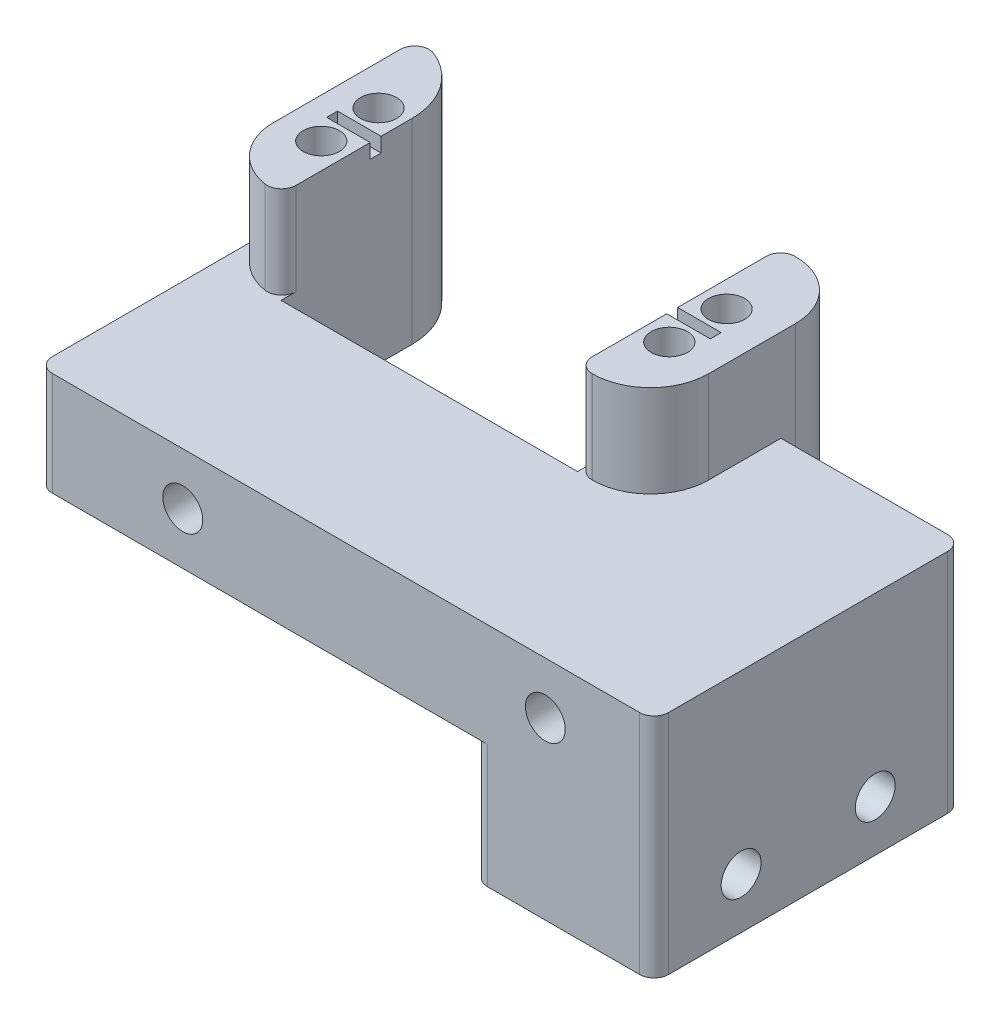
SolidWorks part; units mm, degrees
ref_plane "Front" through (0, 0, 0) normal (0, 0, 1) x (1, 0, 0)
ref_plane "Top" through (0, 0, 0) normal (0, 1, 0) x (1, 0, 0)
ref_plane "Right" through (0, 0, 0) normal (1, 0, 0) x (0, 0, -1)
sketch "Sketch1" plane through (0, 0, 0) normal (0, 1, 0) x (1, 0, 0)
  line L1 (0, 0) -> (85, 0)
  line L2 (0, 0) -> (0, 52.5)
  line L3 (0, 52.5) -> (85, 52.5)
  line L4 (85, 0) -> (85, 52.5)
  dimension "D1" = 85
  dimension "D2" = 52.5
extrude "Boss-Extrude1" add sketch "Sketch1" along normal blind 27
sketch "Sketch2" plane through (0, 27, 0) normal (0, 1, 0) x (1, 0, 0)
  line L0 (0, 52.5) -> (0, 0) construction
  line L1 (85, 52.5) -> (0, 52.5) construction
  circle A0 centre (5.5, 41.5) radius 2.5
  circle A1 centre (53.5, 41.5) radius 2.5
  circle A2 centre (53.5, 33.6) radius 2.5
  circle A3 centre (5.5, 33.6) radius 2.5
  dimension "D3" = 5
  dimension "D6" = 48
  dimension "D1" = 5.5
  dimension "D2" = 11
  dimension "D7" = 7.9
  dimension "D4" = 2
  dimension "D5" = 2
extrude "Cut-Extrude1" cut sketch "Sketch2" against normal through all
sketch "Sketch4" plane through (0, 0, 0) normal (-1, 0, 0) x (0, 0, 1)
  line L0 (-52.5, 27) -> (0, 27) construction
  line L1 (0, 27) -> (-24.5, 27)
  line L2 (0, 27) -> (0, 14.3)
  line L3 (0, 14.3) -> (-24.5, 14.3)
  line L4 (-24.5, 27) -> (-24.5, 14.3)
  line L5 (0, 27) -> (0, 0) construction
  dimension "D1" = 12.7
  dimension "D2" = 24.5
extrude "Cut-Extrude2" cut sketch "Sketch4" against normal through all
sketch "Sketch5" plane through (0, 0, -24.5) normal (0, 0, 1) x (1, 0, 0)
  line L0 (85, 14.3) -> (0, 14.3) construction
  line L1 (85, 27) -> (60, 27)
  line L2 (85, 27) -> (85, 14.3)
  line L3 (85, 14.3) -> (60, 14.3)
  line L4 (60, 27) -> (60, 14.3)
  dimension "D1" = 25
extrude "Cut-Extrude3" cut sketch "Sketch5" against normal through all
sketch "Sketch6" plane through (0, 27, 0) normal (0, 1, 0) x (1, 0, 0)
  line L0 (60, 24.5) -> (0, 24.5) construction
  line L1 (9.05, 24.5) -> (49.95, 24.5)
  line L2 (9.05, 24.5) -> (9.05, 52.5)
  line L3 (9.05, 52.5) -> (49.95, 52.5)
  line L4 (49.95, 24.5) -> (49.95, 52.5)
  line L5 (60, 52.5) -> (0, 52.5) construction
  line L6 (29.5, 41.5) -> (29.5, 52.5) construction
  line L7 (5.5, 41.5) -> (53.5, 41.5) construction
  circle A0 centre (5.5, 41.5) radius 2.5 construction
  dimension "D1" = 3.55
extrude "Cut-Extrude4" cut sketch "Sketch6" against normal through all
fillet "Fillet1" radius 10 1 edges at (9.05, 13.5, -52.5)
fillet "Fillet2" radius 8 3 edges at (60, 20.65, -52.5) (0, 20.65, -24.5) (60, 20.65, -24.5)
fillet "Fillet4" radius 2 7 edges at (9.05, 20.65, -24.5) (49.95, 20.65, -24.5) (49.95, 13.5, -52.5) (85, 7.15, -52.5) (85, 7.15, 0) (0, 7.15, 0) (0, 13.5, -52.5)
sketch "Sketch7" plane through (0, 0, 0) normal (0, 0, 1) x (1, 0, 0)
  line L0 (20, 0) -> (20, 14.3) construction
  line L1 (2, 0) -> (83, 0) construction
  line L2 (83, 14.3) -> (2, 14.3) construction
  line L3 (85, 14.3) -> (85, 0) construction
  circle A0 centre (70, 7.15) radius 2.75
  circle A1 centre (20, 7.15) radius 2.75
  dimension "D3" = 5.5
  dimension "D1" = 50
  dimension "D2" = 15
extrude "Cut-Extrude5" cut sketch "Sketch7" against normal through all
sketch "Sketch8" plane through (0, 27, 0) normal (0, 1, 0) x (1, 0, 0)
  line L0 (9.05, 42.5452) -> (9.05, 26.5757) construction
  line L1 (3.05, 38.3) -> (9.05, 38.3)
  line L2 (3.05, 38.3) -> (3.05, 36.8)
  line L3 (3.05, 36.8) -> (9.05, 36.8)
  line L4 (9.05, 38.3) -> (9.05, 36.8)
  line L5 (5.5, 39) -> (5.5, 36.1) construction
  line L6 (5.5, 37.55) -> (9.05, 37.55) construction
  line L7 (49.95, 26.5) -> (49.95, 50.5) construction
  line L8 (49.95, 36.8) -> (55.95, 36.8)
  line L9 (49.95, 36.8) -> (49.95, 38.3)
  line L10 (49.95, 38.3) -> (55.95, 38.3)
  line L11 (55.95, 36.8) -> (55.95, 38.3)
  circle A0 centre (5.5, 41.5) radius 2.5 construction
  circle A1 centre (5.5, 33.6) radius 2.5 construction
  dimension "D1" = 1.5
  dimension "D2" = 6
extrude "Cut-Extrude6" cut sketch "Sketch8" against normal blind 2
sketch "Sketch9" plane through (0, 14.3, 0) normal (0, 1, 0) x (1, 0, 0)
  line L0 (85, 50.5) -> (85, 2) construction
  line L1 (85, 42.5) -> (60, 42.5)
  line L2 (85, 42.5) -> (85, 52.5)
  line L3 (85, 52.5) -> (83, 52.5)
  line L4 (60, 42.5) -> (60, 44.5)
  line L5 (52, 52.5) -> (83, 52.5) construction
  line L6 (52, 52.5) -> (83, 52.5)
  arc A0 (60, 44.5) -> (52, 52.5) centre (52, 44.5) ccw construction
  arc A1 (60, 44.5) -> (52, 52.5) centre (52, 44.5) ccw
  point P6 (60.7979, 52.3027)
  point P7 (61.1036, 52.5)
  point P12 (82.7563, 52.5)
  dimension "D1" = 10
extrude "Cut-Extrude7" cut sketch "Sketch9" against normal through all
sketch "Sketch10" plane through (0, 0, 0) normal (0, -1, 0) x (1, 0, 0)
  line L0 (2, 0) -> (83, 0) construction
  line L1 (85, -42.5) -> (60, -42.5)
  line L2 (85, -42.5) -> (85, -2)
  line L3 (83, 0) -> (60, 0)
  line L4 (60, -42.5) -> (60, 0)
  line L5 (60, -44.5) -> (60, -42.5) construction
  arc A0 (85, -2) -> (83, 0) centre (83, -2) ccw
  dimension "D1" = 2
extrude "Boss-Extrude2" add sketch "Sketch10" along normal blind 17
sketch "Sketch11" plane through (85, 0, 0) normal (1, 0, 0) x (0, 0, -1)
  line L0 (42.5, -17) -> (42.5, 14.3) construction
  line L2 (0, -17) -> (0, 14.3) construction
  line L3 (42.5, -17) -> (2, -17) construction
  circle A0 centre (30.5, -10) radius 2.75
  circle A1 centre (12, -10) radius 2.75
  point P4 (0, 0)
  dimension "D4" = 5.5
  dimension "D1" = 12
  dimension "D2" = 12
  dimension "D3" = 7
extrude "Cut-Extrude8" cut sketch "Sketch11" against normal through all
fillet "Fillet5" radius 2 3 edges at (85, -1.35, -42.5) (60, -8.5, 0) (60, -8.5, -42.5)
